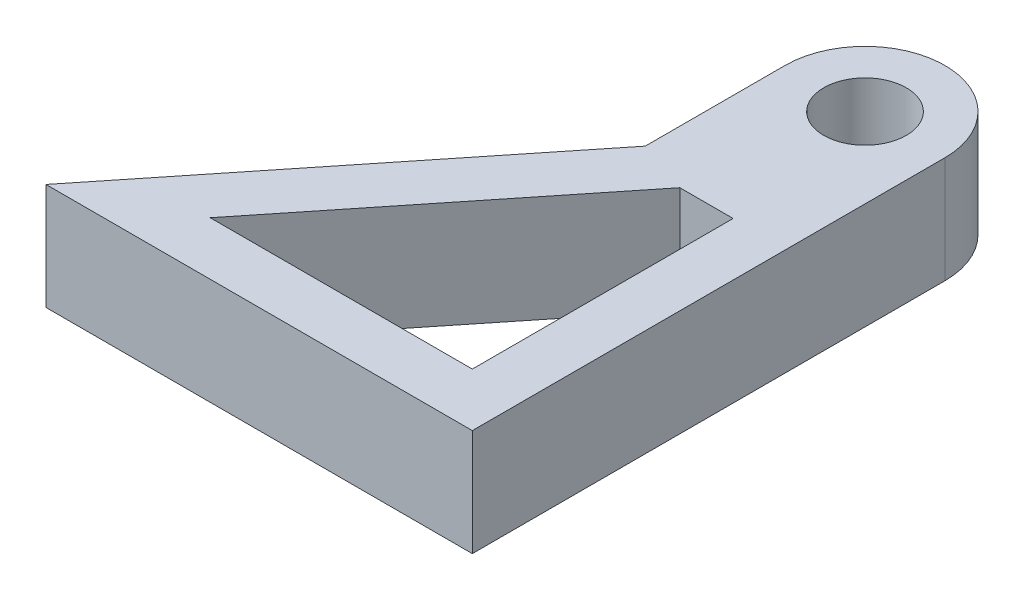
SolidWorks part; units mm, degrees
ref_plane "Front Plane" through (0, 0, 0) normal (0, 0, 1) x (1, 0, 0)
ref_plane "Top Plane" through (0, 0, 0) normal (0, 1, 0) x (1, 0, 0)
ref_plane "Right Plane" through (0, 0, 0) normal (1, 0, 0) x (0, 0, -1)
sketch "Sketch1" plane through (0, 0, 0) normal (0, 1, 0) x (1, 0, 0)
  line L1 (-15, 0) -> (-15.007, -26.2383)
  line L2 (-65.0017, -88.6925) -> (15, -88.6925)
  line L4 (-65.0017, -88.6925) -> (-15.007, -26.2383)
  line L6 (15, -88.6925) -> (15, 0)
  circle A0 centre (0, 0) radius 7.75
  arc A1 (15, 0) -> (-15, 0) centre (0, -0.004) ccw
  dimension "D1" = 15.5
  dimension "D3" = 80
extrude "Boss-Extrude1" add sketch "Sketch1" along normal blind 20
sketch "Sketch2" plane through (0, 20, 0) normal (0, 1, 0) x (1, 0, 0)
  line L0 (-65.0017, -88.6925) -> (15, -88.6925) construction
  line L1 (15, 0) -> (-15, 0)
  line L2 (15, 0) -> (15, -88.6925)
  line L3 (15, -88.6925) -> (-15, -88.6925)
  line L4 (-15, 0) -> (-15, -88.6925)
  dimension "D1" = 30
ref_point "Point1"
sketch "Sketch3" plane through (0, 0, 0) normal (0, -1, 0) x (1, 0, 0)
  line L4 (5, 29.749) -> (-5.0079, 29.749)
  line L8 (-44.1873, 78.6925) -> (-5.0079, 29.749)
  line L9 (-5.0079, 29.749) -> (-5, 0.0026)
  line L10 (5, 0) -> (5, 78.6925)
  line L11 (5, 78.6925) -> (-44.1873, 78.6925)
  line L12 (-44.1873, 78.6925) -> (-5.0079, 29.749)
  line L14 (5, 29.749) -> (5, 78.6925)
  line L15 (5, 78.6925) -> (-44.1873, 78.6925)
  arc A2 (-5, 0.0026) -> (5, 0) centre (0, 0.004) ccw
  dimension "D1" = 10
extrude "Cut-Extrude1" cut sketch "Sketch3" against normal blind 37
